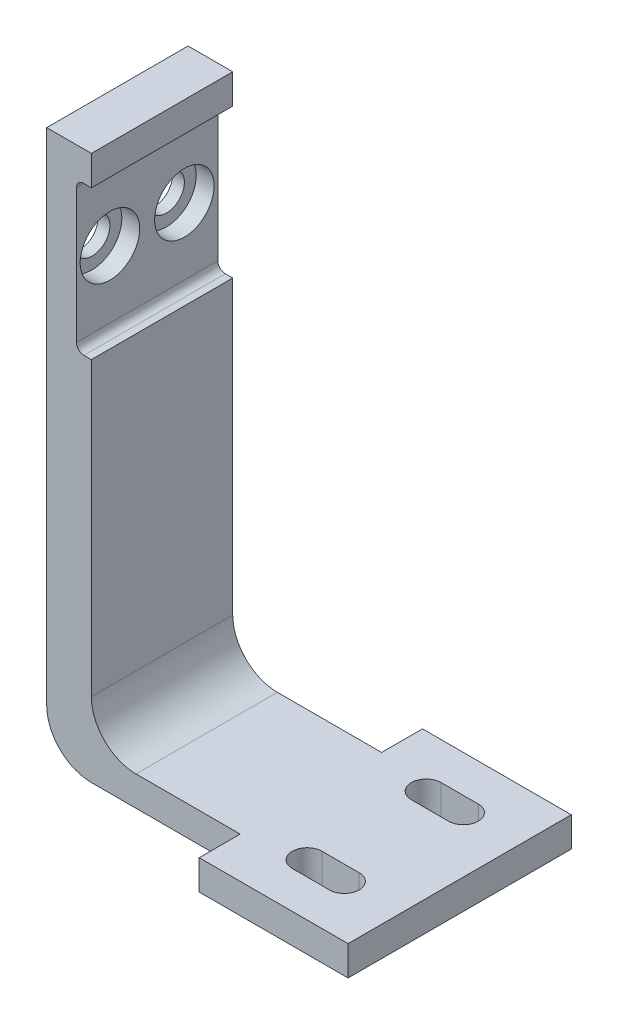
SolidWorks part; units mm, degrees
material "6061-T6 (SS)"
ref_plane "Front Plane" through (0, 0, 0) normal (0, 0, 1) x (1, 0, 0)
ref_plane "Top Plane" through (0, 0, 0) normal (0, 1, 0) x (1, 0, 0)
ref_plane "Right Plane" through (0, 0, 0) normal (1, 0, 0) x (0, 0, -1)
sketch "Sketch1" plane through (0, 0, 0) normal (0, 0, 1) x (1, 0, 0)
  line L0 (-15.4886, 21.5) -> (-17.5374, 21.5) construction
  line L9 (-17.5374, 16.5) -> (-17.5374, 26.5)
  line L10 (-19.5374, 0) -> (-19.5374, 28.5)
  line L11 (-19.5374, 28.5) -> (-16.5374, 28.5)
  line L12 (-16.5374, 28.5) -> (-16.5374, 26.5)
  line L17 (-12.4274, -6.11) -> (3.4626, -6.11)
  line L18 (3.4626, -6.11) -> (3.4626, -8.11)
  line L19 (3.4626, -8.11) -> (-11.4274, -8.11)
  line L20 (-17.5374, 26.5) -> (-16.5374, 26.5)
  line L21 (-17.5374, 16.5) -> (-16.5374, 16.5)
  line L22 (-16.5374, 16.5) -> (-16.5374, 13.5)
  line L23 (-19.5374, 0) -> (-19.5374, -8.11)
  line L24 (-19.5374, -8.11) -> (-11.4274, -8.11)
  line L25 (-16.5374, 13.5) -> (-16.5374, -6.11)
  line L26 (-16.5374, -6.11) -> (-12.4274, -6.11)
  line L29 (-12.4274, -6.11) -> (-10.0144, -6.11) construction
  point P15 (-17.5374, 21.5)
  point P21 (-12.4274, 0)
  dimension "D3" = 36.61
  dimension "D4" = 3
  dimension "D2" = 3
  dimension "D5" = 23
  dimension "D6" = 10
  dimension "D7" = 2
  dimension "D8" = 1
  dimension "D10" = 2
extrude "Boss-Extrude1" add sketch "Sketch1" along normal mid plane 9.5
sketch "Sketch2" plane through (-17.5374, 0, 0) normal (1, 0, 0) x (0, 0, -1)
  line L0 (-4.75, 21.5) -> (4.75, 21.5) construction
  line L1 (-4.75, 16.5) -> (-4.75, 26.5) construction
  line L2 (4.75, 16.5) -> (4.75, 26.5) construction
  point P8 (-2.5, 21.5)
  point P9 (0, 21.5)
  point P11 (2.5, 21.5)
  dimension "D2" = 2.5
  dimension "D1" = 2.5
hole_wizard "M2 Clearance Hole1" positions "3DSketch1" profile "Sketch3" hole size "M2" standard "ANSI Metric" end condition through all
sketch3d "3DSketch1"
  point P0 (-17.5374, 21.5, 2.5)
  point P3 (-17.5374, 21.5, -2.5)
sketch "Sketch3" plane through (-17.5374, 21.5, 2.5) normal (0, 1, 0) x (0, 0, -1)
  line L0 (0, 0) -> (0, 2)
  line L1 (0, 2) -> (1.2, 2)
  line L2 (1.2, 2) -> (1.2, 0)
  line L5 (1.2, 0) -> (0, 0)
  line L11 (0, -6.35) -> (0, 107.95) construction
  dimension "Thru Hole Dia." = 2.4
  dimension "Thru Hole Depth" = 2
sketch "Sketch4" plane through (-17.5374, 0, 0) normal (1, 0, 0) x (0, 0, -1)
  circle A0 centre (-2.5, 21.5) radius 2
  circle A1 centre (2.5, 21.5) radius 2
  dimension "D1" = 4
  dimension "D2" = 4
extrude "Cut-Extrude1" cut sketch "Sketch4" against normal blind 1.2
sketch "Sketch5" plane through (0, -8.11, 0) normal (0, -1, 0) x (1, 0, 0)
  line L0 (3.4626, -7.5) -> (3.4626, 7.5)
  line L1 (3.4626, 4.75) -> (3.4626, -4.75) construction
  line L2 (3.4626, 7.5) -> (-6.5374, 7.5)
  line L3 (-6.5374, 7.5) -> (-6.5374, -7.5)
  line L4 (-6.5374, -7.5) -> (3.4626, -7.5)
  point P3 (3.4626, 0)
  dimension "D1" = 10
  dimension "D2" = 15
extrude "Boss-Extrude2" add sketch "Sketch5" against normal blind 2
sketch "Sketch6" plane through (0, -6.11, 0) normal (0, 1, 0) x (1, 0, 0)
  line L0 (3.4626, 0) -> (-6.5374, 0) construction
  line L1 (3.4626, 7.5) -> (3.4626, -7.5) construction
  line L2 (-0.2874, -4) -> (-2.7874, -4) construction
  line L3 (-1.5374, -7.5) -> (-1.5374, 7.5) construction
  line L4 (3.4626, -7.5) -> (-6.5374, -7.5) construction
  line L5 (-6.5374, 7.5) -> (3.4626, 7.5) construction
  line L6 (-0.2874, -5) -> (-2.7874, -5)
  line L7 (-0.2874, -3) -> (-2.7874, -3)
  line L8 (-0.2874, 4) -> (-2.7874, 4) construction
  line L9 (-0.2874, 5) -> (-2.7874, 5)
  line L10 (-0.2874, 3) -> (-2.7874, 3)
  arc A0 (-0.2874, -5) -> (-0.2874, -3) centre (-0.2874, -4) ccw
  arc A1 (-2.7874, -3) -> (-2.7874, -5) centre (-2.7874, -4) ccw
  arc A2 (-0.2874, 5) -> (-0.2874, 3) centre (-0.2874, 4) cw
  arc A3 (-2.7874, 3) -> (-2.7874, 5) centre (-2.7874, 4) cw
  point P12 (-1.5374, -4)
  point P13 (-1.5374, 0)
  point P14 (-1.5374, 4)
  point P15 (-1.5374, -4)
  point P23 (-1.5374, 4)
  dimension "D3" = 1
  dimension "D1" = 4
  dimension "D2" = 2.5
extrude "Cut-Extrude2" cut sketch "Sketch6" against normal up to surface (2 mm away) up to face at (-7.2874, -8.11, 0)
fillet "Fillet1" radius 3 2 edges at (-16.5374, -6.11, 0) (-19.5374, -8.11, 0)
fillet "Fillet2" radius 0.5 2 edges at (-17.5374, 16.5, 0) (-17.5374, 26.5, 0)
